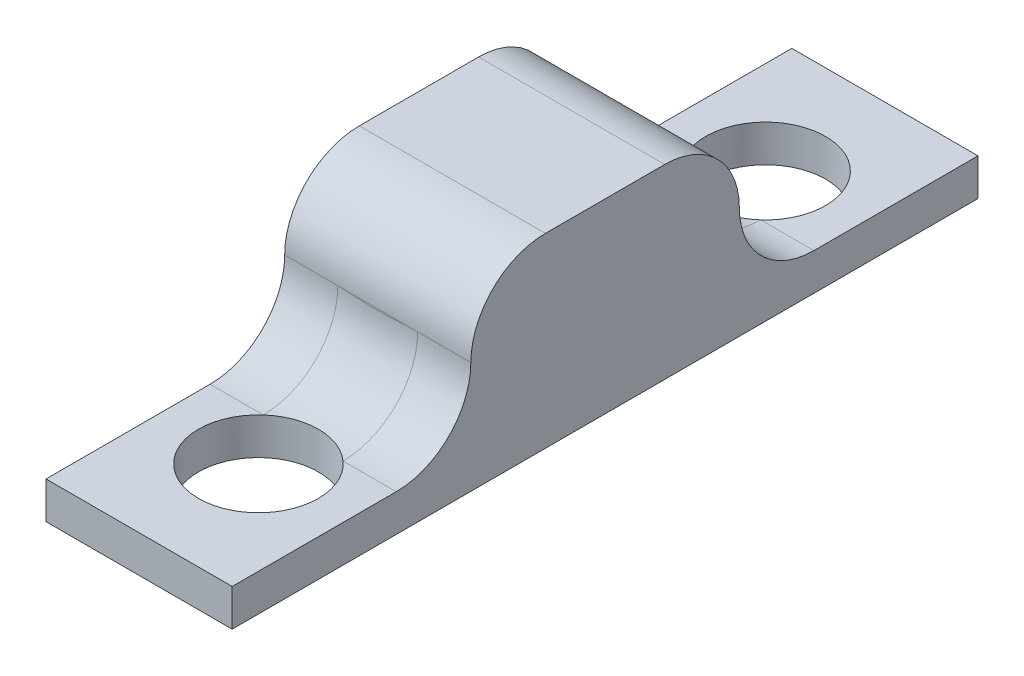
SolidWorks part; units mm, degrees
ref_plane "Front" through (0, 0, 0) normal (0, 0, 1) x (1, 0, 0)
ref_plane "Top" through (0, 0, 0) normal (0, 1, 0) x (1, 0, 0)
ref_plane "Right" through (0, 0, 0) normal (1, 0, 0) x (0, 0, -1)
sketch "Sketch1" plane through (0, 0, 0) normal (1, 0, 0) x (0, 0, -1)
  line L1 (-15.875, -3.9624) -> (15.875, -3.9624)
  line L2 (-15.875, -3.9624) -> (-15.875, 3.9624)
  line L3 (-15.875, 3.9624) -> (15.875, 3.9624)
  line L4 (15.875, -3.9624) -> (15.875, 3.9624)
  line L5 (-15.875, -3.9624) -> (15.875, 3.9624) construction
  line L6 (-15.875, 3.9624) -> (15.875, -3.9624) construction
  point P0 (0, 0)
  dimension "D1" = 31.75
  dimension "D2" = 7.9248
extrude "Boss-Extrude1" add sketch "Sketch1" along normal blind 7.9248
sketch "Sketch2" plane through (0, -3.9624, 0) normal (0, -1, 0) x (1, 0, 0)
  line L0 (0, 3.2385) -> (6.477, 3.2385)
  line L1 (0, 15.875) -> (0, -15.875) construction
  line L2 (6.477, 3.2385) -> (6.477, -3.2385)
  line L3 (6.477, -3.2385) -> (0, -3.2385)
  line L4 (0, -3.2385) -> (0, 3.2385)
  point P4 (6.477, 0)
  dimension "D1" = 6.477
  dimension "D2" = 6.477
extrude "Cut-Extrude1" cut sketch "Sketch2" against normal blind 6.477
sketch "Sketch3" plane through (0, 3.9624, 0) normal (0, 1, 0) x (1, 0, 0)
  line L6 (7.9248, 15.875) -> (7.9248, -15.875) construction
  line L7 (0, 15.875) -> (7.9248, 15.875)
  line L8 (0, 15.875) -> (0, 5.715)
  line L9 (0, 5.715) -> (7.9248, 5.715)
  line L10 (7.9248, 15.875) -> (7.9248, 5.715)
  line L11 (6.477, 0) -> (7.9248, 0) construction
  line L12 (6.477, 3.2385) -> (6.477, -3.2385) construction
  line L13 (0, -15.875) -> (0, -5.715)
  line L14 (0, -15.875) -> (7.9248, -15.875)
  line L15 (7.9248, -15.875) -> (7.9248, -5.715)
  line L16 (0, -5.715) -> (7.9248, -5.715)
  dimension "D1" = 10.16
extrude "Cut-Extrude2" cut sketch "Sketch3" against normal blind 6.35
sketch "Sketch4" plane through (0, -2.3876, 0) normal (0, 1, 0) x (1, 0, 0)
  line L2 (3.9624, -5.715) -> (3.9624, -15.875) construction
  line L3 (7.9248, -5.715) -> (0, -5.715) construction
  line L4 (0, -15.875) -> (7.9248, -15.875) construction
  line L5 (0, 0) -> (7.9248, 0) construction
  line L6 (7.9248, 5.715) -> (7.9248, -5.715) construction
  circle A0 centre (3.9624, -10.795) radius 2.5527
  circle A1 centre (3.9624, 10.795) radius 2.5527
  point P9 (3.9624, -10.795)
  dimension "D1" = 5.1054
extrude "Cut-Extrude3" cut sketch "Sketch4" against normal through all both and the other way through all
fillet "Fillet1" radius 3.175 2 edges at (3.9624, -2.3876, 5.715) (3.9624, -2.3876, -5.715)
fillet "Fillet2" radius 3.175 2 edges at (3.9624, 3.9624, -5.715) (3.9624, 3.9624, 5.715)
fillet "Fillet3" radius 3.175 2 edges at (3.2385, 2.5146, -3.2385) (3.2385, 2.5146, 3.2385)
